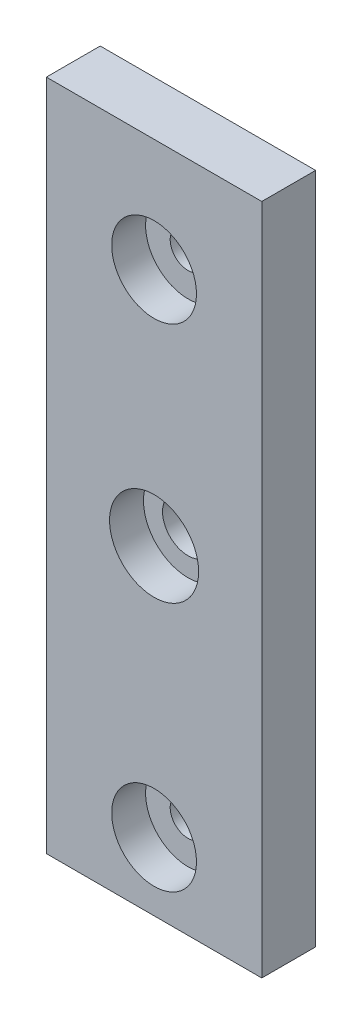
SolidWorks part; units mm, degrees
material "PTFE (general)"
ref_plane "Front Plane" through (0, 0, 0) normal (0, 0, 1) x (1, 0, 0)
ref_plane "Top Plane" through (0, 0, 0) normal (0, 1, 0) x (1, 0, 0)
ref_plane "Right Plane" through (0, 0, 0) normal (1, 0, 0) x (0, 0, -1)
sketch "Sketch1" plane through (0, 0, 0) normal (0, 1, 0) x (1, 0, 0)
  line L1 (19.7561, -3.1163) -> (45.1561, -3.1163)
  line L2 (19.7561, -3.1163) -> (19.7561, 3.2337)
  line L3 (19.7561, 3.2337) -> (45.1561, 3.2337)
  line L4 (45.1561, -3.1163) -> (45.1561, 3.2337)
  dimension "D1" = 25.4
  dimension "D2" = 6.35
extrude "Boss-Extrude1" add sketch "Sketch1" along normal blind 100
sketch "Sketch2" plane through (0, 0, 3.1163) normal (0, 0, 1) x (1, 0, 0)
  line L0 (32.4561, 100) -> (32.4561, 0) construction
  line L1 (19.7561, 100) -> (45.1561, 100) construction
  line L2 (19.7561, 0) -> (45.1561, 0) construction
  circle A0 centre (32.4561, 81.7) radius 2.1
  circle A1 centre (32.4561, 23.71) radius 2.1
  circle A2 centre (32.4561, 81.7) radius 5
  circle A3 centre (32.4561, 23.71) radius 5
  dimension "D1" = 81.7
  dimension "D2" = 23.71
  dimension "D3" = 4.2
  dimension "D4" = 4.2
  dimension "D5" = 10
  dimension "D6" = 10
extrude "Cut-Extrude1" cut sketch "Sketch2" against normal through all contours A0 | A1
extrude "Cut-Extrude2" cut sketch "Sketch2<3>" against normal blind 4 contours A2
sketch "Sketch2<3>" plane through (0, 0, 3.1163) normal (0, 0, 1) x (1, 0, 0) same geometry as "Sketch2"
extrude "Cut-Extrude3" cut sketch "Sketch2<4>" against normal blind 4 contours A3
sketch "Sketch2<4>" plane through (0, 0, 3.1163) normal (0, 0, 1) x (1, 0, 0) same geometry as "Sketch2"
sketch "Sketch5" plane through (0, 0, 3.1163) normal (0, 0, 1) x (1, 0, 0)
  line L0 (45.1561, 100) -> (45.1561, 0) construction
  line L1 (19.7561, 100) -> (45.1561, 100)
  line L2 (19.7561, 100) -> (19.7561, 95)
  line L3 (19.7561, 95) -> (45.1561, 95)
  line L4 (45.1561, 100) -> (45.1561, 95)
  line L6 (19.7561, 0) -> (45.1561, 0)
  line L7 (19.7561, 0) -> (19.7561, 12)
  line L8 (19.7561, 12) -> (45.1561, 12)
  line L9 (45.1561, 0) -> (45.1561, 12)
  dimension "D1" = 5
  dimension "D2" = 12
extrude "Cut-Extrude4" cut sketch "Sketch5" against normal through all
sketch "Sketch6" plane through (0, 0, 3.1163) normal (0, 0, 1) x (1, 0, 0)
  line L0 (32.4561, 95) -> (32.4561, 12) construction
  line L1 (19.7561, 95) -> (45.1561, 95) construction
  line L2 (45.1561, 12) -> (19.7561, 12) construction
  circle A0 centre (32.4561, 53.471) radius 5.25
  dimension "D2" = 10.5
  dimension "D1" = 41.529
extrude "Cut-Extrude5" cut sketch "Sketch6" against normal through all contours A0
sketch "Sketch7" plane through (0, 0, 3.1163) normal (0, 0, 1) x (1, 0, 0)
  line L0 (45.1561, 95) -> (45.1561, 12) construction
  line L1 (19.7561, 12) -> (45.1561, 12)
  line L2 (19.7561, 12) -> (19.7561, 15.7)
  line L3 (19.7561, 15.7) -> (45.1561, 15.7)
  line L4 (45.1561, 12) -> (45.1561, 15.7)
  dimension "D1" = 3.7
extrude "Cut-Extrude6" cut sketch "Sketch7" against normal through all
sketch "Sketch8" plane through (0, 0, -3.2337) normal (0, 0, -1) x (-1, 0, 0)
  circle A0 centre (-32.4561, 53.471) radius 3
  circle A1 centre (-32.4561, 53.471) radius 5.25 construction
  circle A2 centre (-32.4561, 53.471) radius 5.25
extrude "Boss-Extrude2" add sketch "Sketch8" against normal blind 2.35
